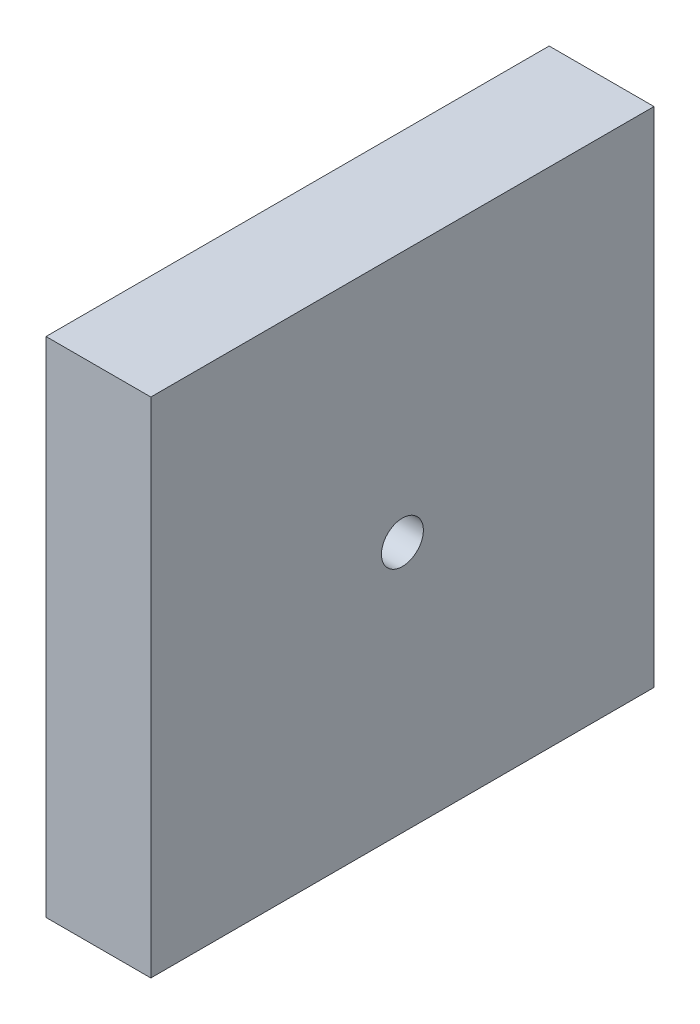
SolidWorks part; units mm, degrees
material "Tungsten"
ref_plane "Ebene vorne" through (0, 0, 0) normal (0, 0, 1) x (1, 0, 0)
ref_plane "Ebene oben" through (0, 0, 0) normal (0, 1, 0) x (1, 0, 0)
ref_plane "Ebene rechts" through (0, 0, 0) normal (1, 0, 0) x (0, 0, -1)
sketch "Sketch2" plane through (0, 0, 0) normal (1, 0, 0) x (0, 0, -1)
  line L0 (0, 48) -> (0, -48) construction
  line L1 (-48, 48) -> (48, 48)
  line L2 (-48, 48) -> (-48, -48)
  line L3 (-48, -48) -> (48, -48)
  line L4 (48, 48) -> (48, -48)
  line L5 (-48, 0) -> (48, 0) construction
  circle A0 centre (0, 0) radius 4
  dimension "D3" = 8
  dimension "D1" = 96
  dimension "D2" = 96
extrude "Boss-Extrude1" add sketch "Sketch2" along normal blind 20
